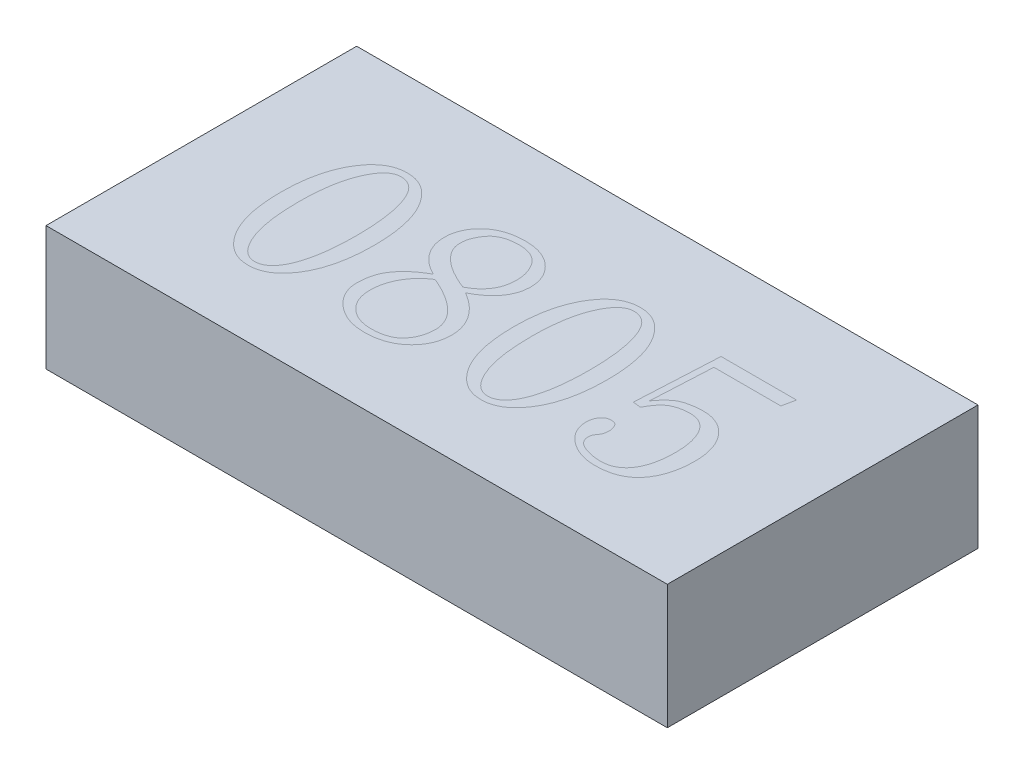
SolidWorks part; units mm, degrees
ref_plane "前视基准面" through (0, 0, 0) normal (0, 0, 1) x (1, 0, 0)
ref_plane "上视基准面" through (0, 0, 0) normal (0, 1, 0) x (1, 0, 0)
ref_plane "右视基准面" through (0, 0, 0) normal (1, 0, 0) x (0, 0, -1)
sketch "草图1" plane through (0, 0, 0) normal (0, 1, 0) x (1, 0, 0)
  line L0 (0, 0) -> (2, 0)
  line L1 (2, 0) -> (2, 1)
  line L2 (2, 1) -> (0, 1)
  line L3 (0, 1) -> (0, 0)
  dimension "D1" = 2
  dimension "D2" = 1
extrude "凸台-拉伸1" add sketch "草图1" along normal blind 0.4
sketch "草图2" plane through (0, 0.4, 0) normal (0, 1, 0) x (1, 0, 0)
  line L0 (0, 0.2077) -> (2, 0.2077) construction
  line L1 (0, 1) -> (0, 0) construction
  line L2 (2, 0) -> (2, 1) construction
  text T0 "0805" height 0.5
wrap "包覆1" sketch "草图2" wrap type scribe source sketch "草图2" face at (1, 0.4, -0.5)
